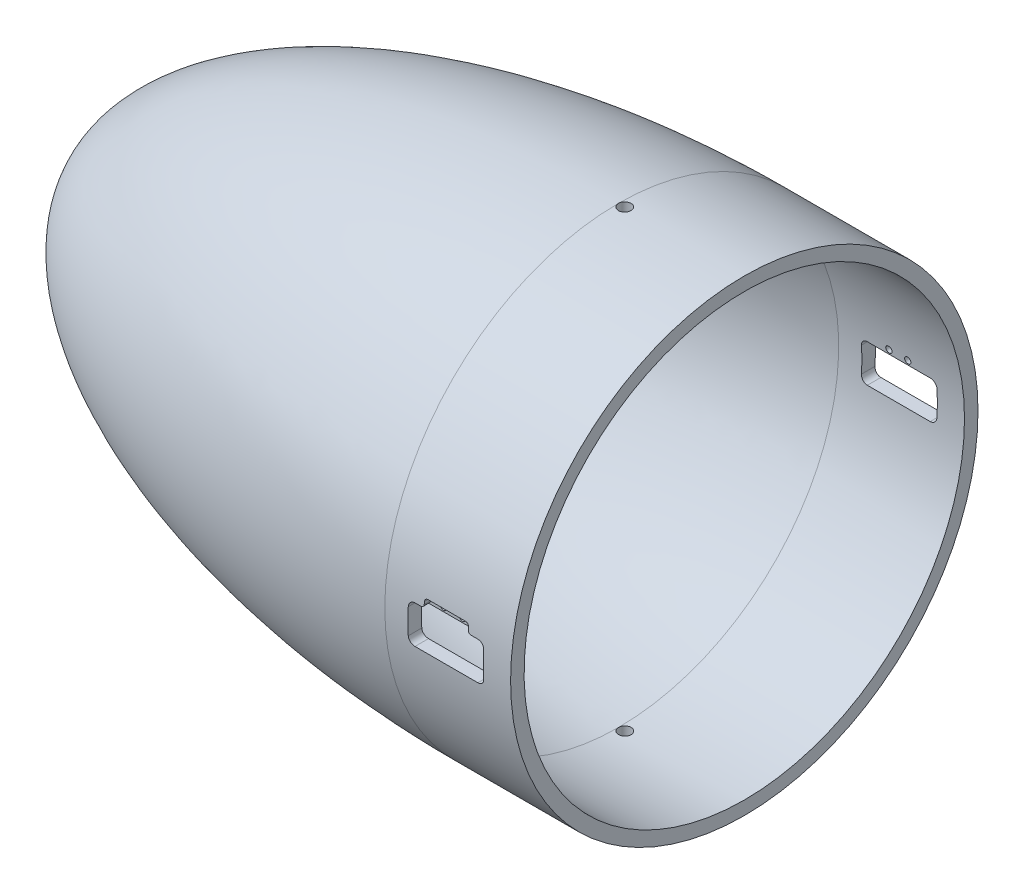
SolidWorks part; units mm, degrees
material "ABS"
ref_plane "Front Plane" through (0, 0, 0) normal (0, 0, 1) x (1, 0, 0)
ref_plane "Top Plane" through (0, 0, 0) normal (0, 1, 0) x (1, 0, 0)
ref_plane "Right Plane" through (0, 0, 0) normal (1, 0, 0) x (0, 0, -1)
sketch "Sketch1" plane through (0, 0, 0) normal (0, 0, 1) x (1, 0, 0)
  line L0 (-83.1361, 0) -> (83.1361, 0) construction
  line L1 (0, 37.1603) -> (0, 35.0138)
  line L2 (-83.1361, 0) -> (-65.5236, 0)
  ellipse E0 centre (0, 0) end of major axis (-83.1361, 0) minor radius 37.1603 (0, 37.1603) -> (-83.1361, 0) ccw
  ellipse E1 centre (2.1955, 4.9445) end of major axis (-65.5236, 0) minor radius 30.1494 (0, 35.0138) -> (-65.5236, 0) ccw
  point P3 (0, 0)
  dimension "D1" = 37.1603
revolve "Revolve3" add sketch "Sketch1" angle 360 about L0
sketch "Sketch2" plane through (0, 0, 0) normal (1, 0, 0) x (0, 0, -1)
  circle A0 centre (0, 0) radius 35.0138
  circle A1 centre (0, 0) radius 37.1603
  dimension "D1" = 74.3206
  dimension "D2" = 2.1465
extrude "Boss-Extrude1" add sketch "Sketch2" along normal blind 20
sketch "Sketch3" plane through (0, 0, 0) normal (0, 1, 0) x (1, 0, 0)
  circle A0 centre (1, 0) radius 1
  dimension "D1" = 2
  dimension "D2" = 1
extrude "Cut-Extrude2" cut sketch "Sketch3" against normal through all both and the other way through all
sketch "Sketch5" plane through (0, 0, 0) normal (0, 0, 1) x (1, 0, 0)
  line L0 (-64.2714, 0) -> (33.86, 0) construction
  line L2 (4.676, 3) -> (14.676, 3)
  line L3 (3.676, 2) -> (3.676, -2)
  line L4 (4.676, -3) -> (14.676, -3)
  line L5 (15.676, 2) -> (15.676, -2)
  line L6 (3.676, 3) -> (15.676, -3) construction
  line L7 (3.676, -3) -> (15.676, 3) construction
  arc A0 (14.676, -3) -> (15.676, -2) centre (14.676, -2) ccw
  arc A1 (15.676, 2) -> (14.676, 3) centre (14.676, 2) ccw
  arc A2 (4.676, -3) -> (3.676, -2) centre (4.676, -2) cw
  arc A3 (4.676, 3) -> (3.676, 2) centre (4.676, 2) ccw
  point P3 (9.676, 0)
  dimension "D3" = 1
  dimension "D1" = 12
  dimension "D2" = 6
extrude "Cut-Extrude3" cut sketch "Sketch5" against normal through all both and the other way through all
sketch "Sketch6" plane through (0, 0, 0) normal (0, 0, 1) x (1, 0, 0)
  line L0 (9.676, 3) -> (9.676, 8.4102) construction
  line L1 (4.676, 3) -> (14.676, 3) construction
  circle A0 centre (11.176, 3.7) radius 0.5
  circle A1 centre (8.176, 3.7) radius 0.5
  dimension "D3" = 1
  dimension "D1" = 1.5
  dimension "D2" = 0.7
extrude "Cut-Extrude4" cut sketch "Sketch6" against normal through all both and the other way through all
sketch "Sketch7" plane through (0, 0, 0) normal (0, 0, 1) x (1, 0, 0)
  line L0 (6.1061, 3) -> (6.1061, 4.35)
  line L1 (4.676, 3) -> (14.676, 3) construction
  line L2 (6.1061, 4.35) -> (13.1061, 4.35)
  line L3 (9.6061, 4.35) -> (9.6061, 2.4711) construction
  line L4 (13.1061, 3) -> (13.1061, 4.35)
  line L5 (6.1061, 3) -> (13.1061, 3)
  dimension "D1" = 3.5
  dimension "D2" = 1.35
extrude "Cut-Extrude5" cut sketch "Sketch7" against normal blind 34 from offset 70
fillet "Fillet1" radius 0.5 1 edges at (6.1061, 3, 36.5195)
fillet "Fillet2" radius 0.5 1 edges at (6.1061, 4.35, 36.4524)
fillet "Fillet3" radius 0.5 1 edges at (13.1061, 4.35, 36.4524)
fillet "Fillet4" radius 0.5 1 edges at (13.1061, 3, 36.5195)
sketch "Sketch9" plane through (0, 0, 0) normal (1, 0, 0) x (0, 0, -1)
  circle A0 centre (0, 0) radius 35.0138
  circle A1 centre (0, 0) radius 37.1603
